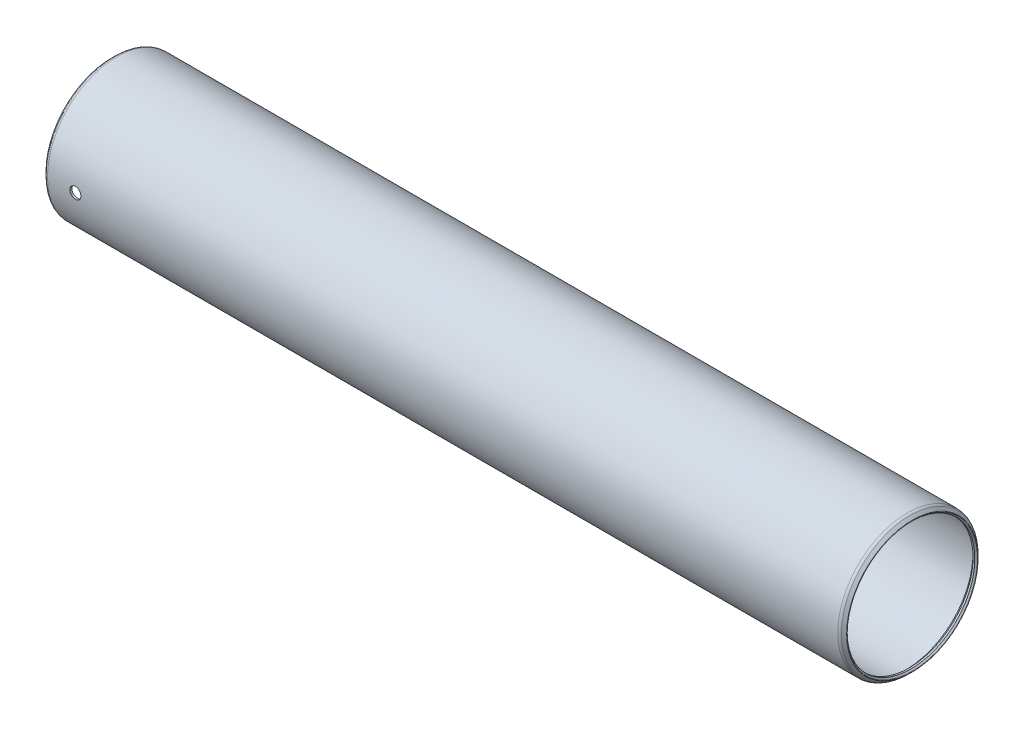
SolidWorks part; units mm, degrees
material "Cast Alloy Steel"
ref_plane "Front Plane" through (0, 0, 0) normal (0, 0, 1) x (1, 0, 0)
ref_plane "Top Plane" through (0, 0, 0) normal (0, 1, 0) x (1, 0, 0)
ref_plane "Right Plane" through (0, 0, 0) normal (1, 0, 0) x (0, 0, -1)
ref_plane "Plane1" through (226.1362, 0, 0) normal (1, 0, 0) x (0, 0, -1)
sketch "Sketch1" plane through (0, 0, 0) normal (0, 0, 1) x (1, 0, 0)
  line L0 (-0.8826, 18.5547) -> (-0.508, 18.1801)
  line L1 (-0.508, 18.1801) -> (0, 18.1801)
  line L2 (0, 18.1801) -> (1.016, 19.196)
  line L3 (1.016, 19.196) -> (225.1202, 19.196)
  line L4 (225.1202, 19.196) -> (226.1362, 18.1801)
  line L5 (226.1362, 18.1801) -> (226.6442, 18.1801)
  line L6 (226.6442, 18.1801) -> (227.0188, 18.5547)
  line L7 (227.0188, 18.7343) -> (226.2831, 19.47)
  line L8 (225.5647, 19.7675) -> (0.5715, 19.7675)
  line L9 (-0.1469, 19.47) -> (-0.8826, 18.7343)
  line L10 (226.1362, 0) -> (0, 0) construction
  arc A0 (-0.8826, 18.7343) -> (-0.8826, 18.5547) centre (-0.7928, 18.6445) ccw
  arc A1 (227.0188, 18.5547) -> (227.0188, 18.7343) centre (226.929, 18.6445) ccw
  arc A2 (226.2831, 19.47) -> (225.5647, 19.7675) centre (225.5647, 18.7515) ccw
  arc A3 (0.5715, 19.7675) -> (-0.1469, 19.47) centre (0.5715, 18.7515) ccw
revolve "Revolve1" add sketch "Sketch1" angle 360 about L10 reverse direction yes
sketch "Sketch2" plane through (0, 0, 0) normal (0, 0, 1) x (1, 0, 0)
  circle A0 centre (8.509, 0) radius 1.5875
extrude "Cut-Extrude1" cut sketch "Sketch2" along normal blind 19.7676
ref_plane "Plane2" through (113.0681, 0, 0) normal (1, 0, 0) x (0, 0, -1)
ref_plane "cp1 XY" through (113.0681, 0, 0) normal (1, 0, 0) x (0, 0, -1)
ref_plane "cp1 XZ" through (0, 19.7676, 0) normal (0, -1, 0) x (1, 0, 0)
ref_plane "cp1 YZ" through (0, 0, 0) normal (0, 0, -1) x (-1, 0, 0)
ref_axis "cp1 X" through (113.0681, 19.7676, 80.9) along (0, 0, -1)
ref_axis "cp1 Y" through (113.0681, -50, 0) along (0, 1, 0)
ref_axis "cp1 Z" through (80.9, 19.7676, 0) along (-1, 0, 0)
sketch3d "cp1"
  point P0 (113.0681, 19.7676, 0)
ref_plane "cp2 XY" through (113.0681, 0, 0) normal (1, 0, 0) x (0, 0, -1)
ref_plane "cp2 XZ" through (0, 0, 0) normal (0, -1, 0) x (1, 0, 0)
ref_plane "cp2 YZ" through (0, 0, -19.7676) normal (0, 0, -1) x (-1, 0, 0)
ref_axis "cp2 X" through (113.0681, 0, 80.9) along (0, 0, -1)
ref_axis "cp2 Y" through (113.0681, -50, -19.7676) along (0, 1, 0)
ref_axis "cp2 Z" through (80.9, 0, -19.7676) along (-1, 0, 0)
sketch3d "cp2"
  point P0 (113.0681, 0, -19.7676)
ref_plane "cp3 XY" through (113.0681, 0, 0) normal (1, 0, 0) x (0, 0, -1)
ref_plane "cp3 XZ" through (0, -19.7676, 0) normal (0, -1, 0) x (1, 0, 0)
ref_plane "cp3 YZ" through (0, 0, 0) normal (0, 0, -1) x (-1, 0, 0)
ref_axis "cp3 X" through (113.0681, -19.7676, 80.9) along (0, 0, -1)
ref_axis "cp3 Y" through (113.0681, -50, 0) along (0, 1, 0)
ref_axis "cp3 Z" through (80.9, -19.7676, 0) along (-1, 0, 0)
sketch3d "cp3"
  point P0 (113.0681, -19.7676, 0)
ref_plane "cp4 XY" through (113.0681, 0, 0) normal (1, 0, 0) x (0, 0, -1)
ref_plane "cp4 XZ" through (0, 0, 0) normal (0, -1, 0) x (1, 0, 0)
ref_plane "cp4 YZ" through (0, 0, 19.7676) normal (0, 0, -1) x (-1, 0, 0)
ref_axis "cp4 X" through (113.0681, 0, 80.9) along (0, 0, -1)
ref_axis "cp4 Y" through (113.0681, -50, 19.7676) along (0, 1, 0)
ref_axis "cp4 Z" through (80.9, 0, 19.7676) along (-1, 0, 0)
sketch3d "cp4"
  point P0 (113.0681, 0, 19.7676)
ref_plane "tube_front XY" through (0, 0, 0) normal (1, 0, 0) x (0, 0, -1)
ref_plane "tube_front XZ" through (0, 0, 0) normal (0, -1, 0) x (1, 0, 0)
ref_plane "tube_front YZ" through (0, 0, 0) normal (0, 0, -1) x (-1, 0, 0)
ref_axis "tube_front X" through (0, 0, 80.9) along (0, 0, -1)
ref_axis "tube_front Y" through (0, -50, 0) along (0, 1, 0)
ref_axis "tube_front Z" through (80.9, 0, 0) along (-1, 0, 0)
sketch3d "tube_front"
  point P0 (0, 0, 0)
ref_plane "tube_rear XY" through (226.1362, 0, 0) normal (1, 0, 0) x (0, 0, -1)
ref_plane "tube_rear XZ" through (0, 0, 0) normal (0, -1, 0) x (1, 0, 0)
ref_plane "tube_rear YZ" through (0, 0, 0) normal (0, 0, -1) x (-1, 0, 0)
ref_axis "tube_rear X" through (226.1362, 0, 80.9) along (0, 0, -1)
ref_axis "tube_rear Y" through (226.1362, -50, 0) along (0, 1, 0)
ref_axis "tube_rear Z" through (80.9, 0, 0) along (-1, 0, 0)
sketch3d "tube_rear"
  point P0 (226.1362, 0, 0)
